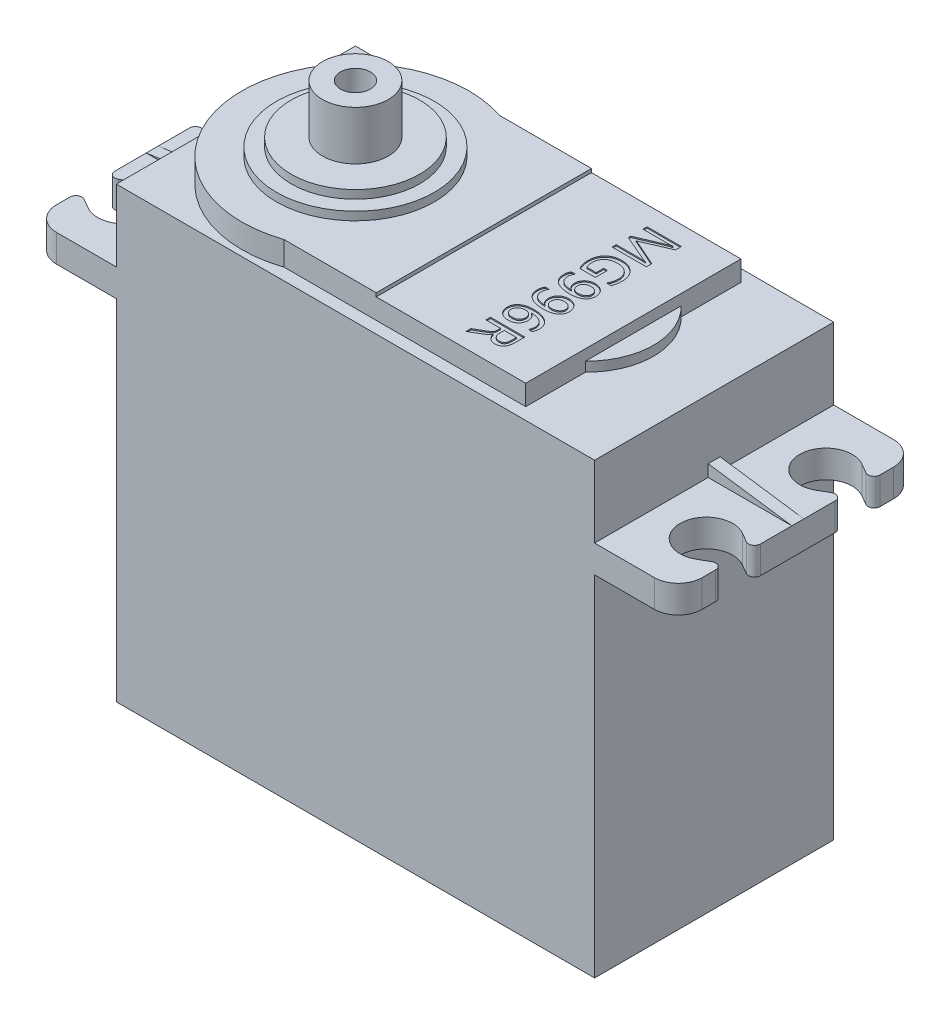
SolidWorks part; units mm, degrees
note: '?' marks a value the reader was unsure of.
ref_plane "前视基准面" through (0, 0, 0) normal (0, 0, 1) x (1, 0, 0)
ref_plane "上视基准面" through (0, 0, 0) normal (0, 1, 0) x (1, 0, 0)
ref_plane "右视基准面" through (0, 0, 0) normal (1, 0, 0) x (0, 0, -1)
other "Configuration Table"
ref_axis "基准轴1" through (0, -21.115, 0) along (0, 1, 0)?
ref_plane "基准面1" through (0, 31.5, 0) normal (0, 1, 0) x (1, 0, 0)
sketch "草图1" plane through (0, 0, 0) normal (0, 1, 0) x (1, 0, 0)
  line L1 (-10, 10) -> (30, 10)
  line L2 (-10, 10) -> (-10, -10)
  line L3 (-10, -10) -> (30, -10)
  line L4 (30, 10) -> (30, -10)
  point P4 (-10, 0)
  dimension "D1" = 40
  dimension "D2" = 20
  dimension "D3" = 10
extrude "凸台-拉伸1" add sketch "草图1" along normal blind 37.5
sketch "草图2" plane through (0, 31.5, 0) normal (0, 1, 0) x (1, 0, 0)
  line L0 (0, 0) -> (-19.0604, 0) construction
  line L1 (-10, 10) -> (-15, 10)
  line L2 (-10, 10) -> (-10, -10)
  line L3 (-10, -10) -> (-15, -10)
  line L5 (10, 15.189) -> (10, -16.2282) construction
  line L6 (-10, -10) -> (30, -10) construction
  line L11 (-17, 8) -> (-17, -8)
  line L12 (37, 8) -> (37, -8)
  line L13 (30, -10) -> (35, -10)
  line L14 (30, 10) -> (30, -10)
  line L15 (30, 10) -> (35, 10)
  arc A0 (-15, 10) -> (-17, 8) centre (-15, 8) ccw
  arc A1 (-15, -10) -> (-17, -8) centre (-15, -8) cw
  arc A2 (35, -10) -> (37, -8) centre (35, -8) ccw
  arc A3 (35, 10) -> (37, 8) centre (35, 8) cw
  point P13 (10, -10)
  dimension "D2" = 2
  dimension "D1" = 7
extrude "凸台-拉伸2" add sketch "草图2" against normal blind 2.3
sketch "草图3" plane through (0, 31.5, 0) normal (0, 1, 0) x (1, 0, 0)
  line L0 (0, 0) -> (-20.7559, 0) construction
  line L1 (10, 12.4142) -> (10, -12.1654) construction
  line L2 (-10, -10) -> (30, -10) construction
  line L3 (-10, 10) -> (-15, 10) construction
  line L4 (-10, -10) -> (-10, 10) construction
  line L5 (-15.45, 6.9053) -> (-16.25, 6.4434)
  line L7 (-16.25, 3.5566) -> (-15.45, 3.0947)
  line L8 (-14.35, 5) -> (-9.9139, 5) construction
  line L10 (-15.45, 6.9053) -> (-15.45, 3.0947)
  line L23 (-17, 8) -> (-17, -8) construction
  line L24 (-17, 6.8764) -> (-17, 3.1236)
  line L25 (-17, -6.8764) -> (-17, -3.1236)
  line L26 (-15.45, -6.9053) -> (-15.45, -3.0947)
  line L27 (-16.25, -3.5566) -> (-15.45, -3.0947)
  line L28 (-15.45, -6.9053) -> (-16.25, -6.4434)
  line L29 (35.45, -6.9053) -> (36.25, -6.4434)
  line L30 (36.25, -3.5566) -> (35.45, -3.0947)
  line L31 (35.45, -6.9053) -> (35.45, -3.0947)
  line L32 (37, -6.8764) -> (37, -3.1236)
  line L33 (37, 6.8764) -> (37, 3.1236)
  line L34 (35.45, 6.9053) -> (35.45, 3.0947)
  line L35 (36.25, 3.5566) -> (35.45, 3.0947)
  line L36 (35.45, 6.9053) -> (36.25, 6.4434)
  circle A0 centre (-14.35, 5) radius 2.2
  arc A4 (-17, 6.8764) -> (-16.25, 6.4434) centre (-16.5, 6.8764) ccw
  arc A5 (-17, 3.1236) -> (-16.25, 3.5566) centre (-16.5, 3.1236) cw
  arc A6 (-17, -3.1236) -> (-16.25, -3.5566) centre (-16.5, -3.1236) ccw
  arc A7 (-17, -6.8764) -> (-16.25, -6.4434) centre (-16.5, -6.8764) cw
  circle A8 centre (-14.35, -5) radius 2.2
  circle A9 centre (34.35, -5) radius 2.2
  arc A10 (37, -6.8764) -> (36.25, -6.4434) centre (36.5, -6.8764) ccw
  arc A11 (37, -3.1236) -> (36.25, -3.5566) centre (36.5, -3.1236) cw
  arc A12 (37, 3.1236) -> (36.25, 3.5566) centre (36.5, 3.1236) ccw
  arc A13 (37, 6.8764) -> (36.25, 6.4434) centre (36.5, 6.8764) cw
  circle A14 centre (34.35, 5) radius 2.2
  point P9 (10, -10)
  dimension "D1" = 4.4
  dimension "D5" = 0.5
  dimension "D2" = 5
  dimension "D3" = 4.35
  dimension "D4" = 30
extrude "切除-拉伸1" cut sketch "草图3" against normal up to next
sketch "草图5" plane through (0, 0, 0) normal (0, 0, 1) x (1, 0, 0)
  line L0 (-10, 31.5) -> (-10, 32.5)
  line L1 (-10, 32.5) -> (-17, 31.5)
  line L2 (-17, 31.5) -> (-10, 31.5)
  line L3 (-10, 37.5) -> (-10, 31.5) construction
  line L4 (55, 31.5) -> (-55, 31.5) construction
  line L6 (-17, 29.2) -> (-17, 31.5) construction
  line L7 (10, 37.5) -> (10, 20.3039) construction
  line L8 (-10, 37.5) -> (30, 37.5) construction
  line L9 (37, 31.5) -> (30, 31.5)
  line L10 (30, 32.5) -> (37, 31.5)
  line L11 (30, 31.5) -> (30, 32.5)
  dimension "D1" = 1
extrude "凸台-拉伸3" add sketch "草图5" along normal mid plane 1
sketch "草图8" plane through (0, 37.5, 0) normal (0, 1, 0) x (1, 0, 0)
  line L1 (10.7414, 9) -> (3.0414, 9)
  line L2 (10.7414, 9) -> (10.7414, -9)
  line L3 (10.7414, -9) -> (3.0414, -9)
  line L4 (3.0414, 9) -> (3.0414, -9)
  circle A0 centre (0, 0) radius 9.5
  point P7 (3.0414, 0)
  dimension "D1" = 19
  dimension "D2" = 18
  dimension "D3" = 7.7
extrude "凸台-拉伸4" add sketch "草图8" along normal blind 2 contours L4 A0 | L4 A0 | A0 L3 L2 L1
sketch "草图9" plane through (0, 37.5, 0) normal (0, 1, 0) x (1, 0, 0)
  line L0 (10.7414, 9) -> (10.7414, -9) construction
  line L1 (10.7414, 9) -> (23.2414, 9)
  line L2 (10.7414, 9) -> (10.7414, -9)
  line L3 (10.7414, -9) -> (23.2414, -9)
  line L4 (23.2414, 9) -> (23.2414, -9)
  point P6 (10.7414, 0)
  dimension "D1" = 12.5
extrude "凸台-拉伸5" add sketch "草图9" along normal blind 1.7 contours L2 L1 L4 L3
sketch "草图10" plane through (0, 37.5, 0) normal (0, 1, 0) x (1, 0, 0)
  line L0 (23.2414, -9) -> (23.2414, 9) construction
  line L1 (24.9414, 6.6978) -> (24.9414, -6.3227) construction
  line L2 (23.2414, -9) -> (23.2414, 9) construction
  line L3 (23.2414, 4) -> (23.2414, -4)
  arc A0 (23.2414, 4) -> (23.2414, -4) centre (19.3855, 0) cw
  dimension "D1" = 1.7
  dimension "D2" = 8
extrude "凸台-拉伸6" add sketch "草图10" along normal blind 0.8
sketch "草图11" plane through (0, 39.5, 0) normal (0, 1, 0) x (1, 0, 0)
  circle A0 centre (0, 0) radius 6.6
  dimension "D1" = 13.2
extrude "凸台-拉伸7" add sketch "草图11" along normal blind 0.7
sketch "草图12" plane through (0, 40.2, 0) normal (0, 1, 0) x (1, 0, 0)
  circle A0 centre (0, 0) radius 5.375
  dimension "D1" = 10.75
extrude "凸台-拉伸8" add sketch "草图12" along normal blind 0.7
sketch "草图13" plane through (0, 40.9, 0) normal (0, 1, 0) x (1, 0, 0)
  circle A0 centre (0, 0) radius 2.75
  circle A1 centre (0, 0) radius 1.25
  dimension "D1" = 5.5
  dimension "D2" = 2.5
extrude "凸台-拉伸9" add sketch "草图13" along normal blind 4.1 contours A0 A1
sketch "草图14" plane through (-10, 0, 0) normal (-1, 0, 0) x (0, 0, 1)
  line L1 (-3.5, 6.7) -> (3.5, 6.7)
  line L2 (-3.5, 6.7) -> (-3.5, 4.2)
  line L3 (-3.5, 4.2) -> (3.5, 4.2)
  line L4 (3.5, 6.7) -> (3.5, 4.2)
  line L5 (-10, 0) -> (10, 0) construction
  point P8 (0, 4.2)
  dimension "D1" = 2.5
  dimension "D2" = 7
  dimension "D3" = 4.2
extrude "凸台-拉伸10" add sketch "草图14" along normal blind 5
sketch "草图15" plane through (0, 39.2, 0) normal (0, 1, 0) x (1, 0, 0)
  line L0 (16.9914, 9) -> (16.9914, -9) construction
  line L1 (23.2414, 9) -> (10.7414, 9) construction
  line L2 (10.7414, -9) -> (23.2414, -9) construction
  text T0 "MG996R" font "微软雅黑" height in points 10
extrude "切除-拉伸2" cut sketch "草图15" against normal blind 0.1
